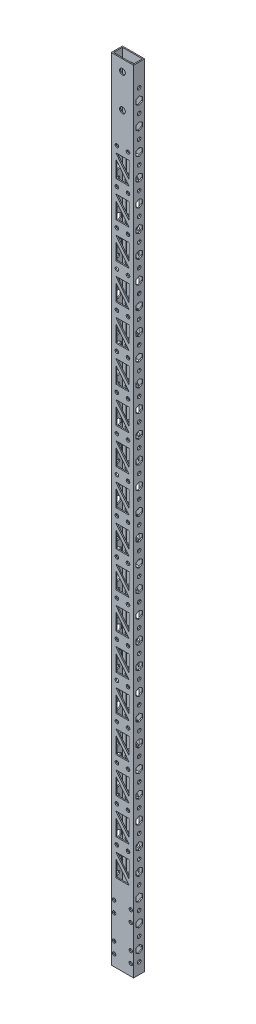
SolidWorks part; units mm, degrees
ref_plane "前视基准面" through (0, 0, 0) normal (0, 0, 1) x (1, 0, 0)
ref_plane "上视基准面" through (0, 0, 0) normal (0, 1, 0) x (1, 0, 0)
ref_plane "右视基准面" through (0, 0, 0) normal (1, 0, 0) x (0, 0, -1)
other "Configuration Table"
sketch "草图1" plane through (0, 0, 0) normal (0, 1, 0) x (1, 0, 0)
  line L1 (-10, -5) -> (10, -5)
  line L2 (-10, -5) -> (-10, 5)
  line L3 (-10, 5) -> (10, 5)
  line L4 (10, -5) -> (10, 5)
  line L5 (-10, -5) -> (10, 5) construction
  line L6 (-10, 5) -> (10, -5) construction
  point P0 (0, 0)
  dimension "D1" = 20
  dimension "D2" = 10
extrude "拉伸-薄壁1" add sketch "草图1" along normal blind 710 thin thin type one direction reverse wall 1
sketch "草图2" plane through (0, 0, -5) normal (0, 0, -1) x (-1, 0, 0)
  line L0 (-10, 710) -> (-10, 0) construction
  line L1 (10, 0) -> (-10, 0) construction
  line L2 (10, 0) -> (10, 30) construction
  line L3 (10, 30) -> (-10, 30) construction
  line L4 (-10, 0) -> (-10, 30) construction
  line L5 (-10, 15) -> (10, 15) construction
  line L6 (0, 0) -> (0, 30) construction
  line L7 (-10, 46.9) -> (10, 46.9) construction
  line L8 (-10, 700) -> (10, 700) construction
  line L9 (10, 710) -> (10, 0) construction
  line L10 (0, 710) -> (0, 700) construction
  line L11 (-10, 710) -> (10, 710) construction
  line L12 (0, 700) -> (0, 670) construction
  circle A0 centre (-7.5, 20) radius 1.55
  circle A1 centre (-7.5, 10) radius 1.55
  circle A2 centre (7.5, 10) radius 1.55
  circle A3 centre (7.5, 20) radius 1.55
  circle A4 centre (-7.5, 51.9) radius 1.55
  circle A5 centre (-7.5, 41.9) radius 1.55
  circle A6 centre (7.5, 41.9) radius 1.55
  circle A7 centre (7.5, 51.9) radius 1.55
  circle A12 centre (0, 700) radius 2.6
  circle A13 centre (0, 670) radius 2.6
  dimension "D2" = 3.1
  dimension "D7" = 5.2
  dimension "D1" = 30
  dimension "D3" = 15
  dimension "D4" = 10
  dimension "D6" = 31.9
  dimension "D8" = 30
  dimension "D10" = 10
  dimension "D5" = 2
extrude "切除-拉伸1" cut sketch "草图2" against normal through all
sketch "草图3" plane through (-10, 0, 0) normal (-1, 0, 0) x (0, 0, 1)
  line L0 (-5, 0) -> (5, 0) construction
  line L1 (0, 10) -> (0, 0) construction
  line L2 (0, 690) -> (0, 670) construction
  line L3 (-3.0311, 681.75) -> (-3.0311, 678.25)
  line L4 (-3.0311, 678.25) -> (0, 676.5)
  line L5 (0, 676.5) -> (3.0311, 678.25)
  line L6 (3.0311, 678.25) -> (3.0311, 681.75)
  line L7 (3.0311, 681.75) -> (0, 683.5)
  line L8 (0, 683.5) -> (-3.0311, 681.75)
  line L9 (3.0311, 661.75) -> (0, 663.5)
  line L10 (0, 663.5) -> (-3.0311, 661.75)
  line L11 (-3.0311, 661.75) -> (-3.0311, 658.25)
  line L12 (-3.0311, 658.25) -> (0, 656.5)
  line L13 (3.0311, 658.25) -> (3.0311, 661.75)
  line L14 (0, 656.5) -> (3.0311, 658.25)
  line L15 (3.0311, 641.75) -> (0, 643.5)
  line L16 (0, 643.5) -> (-3.0311, 641.75)
  line L17 (-3.0311, 641.75) -> (-3.0311, 638.25)
  line L18 (-3.0311, 638.25) -> (0, 636.5)
  line L19 (3.0311, 638.25) -> (3.0311, 641.75)
  line L20 (0, 636.5) -> (3.0311, 638.25)
  line L21 (3.0311, 621.75) -> (0, 623.5)
  line L22 (0, 623.5) -> (-3.0311, 621.75)
  line L23 (-3.0311, 621.75) -> (-3.0311, 618.25)
  line L24 (-3.0311, 618.25) -> (0, 616.5)
  line L25 (3.0311, 618.25) -> (3.0311, 621.75)
  line L26 (0, 616.5) -> (3.0311, 618.25)
  line L27 (3.0311, 601.75) -> (0, 603.5)
  line L28 (0, 603.5) -> (-3.0311, 601.75)
  line L29 (-3.0311, 601.75) -> (-3.0311, 598.25)
  line L30 (-3.0311, 598.25) -> (0, 596.5)
  line L31 (3.0311, 598.25) -> (3.0311, 601.75)
  line L32 (0, 596.5) -> (3.0311, 598.25)
  line L33 (3.0311, 581.75) -> (0, 583.5)
  line L34 (0, 583.5) -> (-3.0311, 581.75)
  line L35 (-3.0311, 581.75) -> (-3.0311, 578.25)
  line L36 (-3.0311, 578.25) -> (0, 576.5)
  line L37 (3.0311, 578.25) -> (3.0311, 581.75)
  line L38 (0, 576.5) -> (3.0311, 578.25)
  line L39 (3.0311, 561.75) -> (0, 563.5)
  line L40 (0, 563.5) -> (-3.0311, 561.75)
  line L41 (-3.0311, 561.75) -> (-3.0311, 558.25)
  line L42 (-3.0311, 558.25) -> (0, 556.5)
  line L43 (3.0311, 558.25) -> (3.0311, 561.75)
  line L44 (0, 556.5) -> (3.0311, 558.25)
  line L45 (3.0311, 541.75) -> (0, 543.5)
  line L46 (0, 543.5) -> (-3.0311, 541.75)
  line L47 (-3.0311, 541.75) -> (-3.0311, 538.25)
  line L48 (-3.0311, 538.25) -> (0, 536.5)
  line L49 (3.0311, 538.25) -> (3.0311, 541.75)
  line L50 (0, 536.5) -> (3.0311, 538.25)
  line L51 (3.0311, 521.75) -> (0, 523.5)
  line L52 (0, 523.5) -> (-3.0311, 521.75)
  line L53 (-3.0311, 521.75) -> (-3.0311, 518.25)
  line L54 (-3.0311, 518.25) -> (0, 516.5)
  line L55 (3.0311, 518.25) -> (3.0311, 521.75)
  line L56 (0, 516.5) -> (3.0311, 518.25)
  line L57 (3.0311, 501.75) -> (0, 503.5)
  line L58 (0, 503.5) -> (-3.0311, 501.75)
  line L59 (-3.0311, 501.75) -> (-3.0311, 498.25)
  line L60 (-3.0311, 498.25) -> (0, 496.5)
  line L61 (3.0311, 498.25) -> (3.0311, 501.75)
  line L62 (0, 496.5) -> (3.0311, 498.25)
  line L63 (3.0311, 481.75) -> (0, 483.5)
  line L64 (0, 483.5) -> (-3.0311, 481.75)
  line L65 (-3.0311, 481.75) -> (-3.0311, 478.25)
  line L66 (-3.0311, 478.25) -> (0, 476.5)
  line L67 (3.0311, 478.25) -> (3.0311, 481.75)
  line L68 (0, 476.5) -> (3.0311, 478.25)
  line L69 (3.0311, 461.75) -> (0, 463.5)
  line L70 (0, 463.5) -> (-3.0311, 461.75)
  line L71 (-3.0311, 461.75) -> (-3.0311, 458.25)
  line L72 (-3.0311, 458.25) -> (0, 456.5)
  line L73 (3.0311, 458.25) -> (3.0311, 461.75)
  line L74 (0, 456.5) -> (3.0311, 458.25)
  line L75 (3.0311, 441.75) -> (0, 443.5)
  line L76 (0, 443.5) -> (-3.0311, 441.75)
  line L77 (-3.0311, 441.75) -> (-3.0311, 438.25)
  line L78 (-3.0311, 438.25) -> (0, 436.5)
  line L79 (3.0311, 438.25) -> (3.0311, 441.75)
  line L80 (0, 436.5) -> (3.0311, 438.25)
  line L81 (3.0311, 421.75) -> (0, 423.5)
  line L82 (0, 423.5) -> (-3.0311, 421.75)
  line L83 (-3.0311, 421.75) -> (-3.0311, 418.25)
  line L84 (-3.0311, 418.25) -> (0, 416.5)
  line L85 (3.0311, 418.25) -> (3.0311, 421.75)
  line L86 (0, 416.5) -> (3.0311, 418.25)
  line L87 (3.0311, 401.75) -> (0, 403.5)
  line L88 (0, 403.5) -> (-3.0311, 401.75)
  line L89 (-3.0311, 401.75) -> (-3.0311, 398.25)
  line L90 (-3.0311, 398.25) -> (0, 396.5)
  line L91 (3.0311, 398.25) -> (3.0311, 401.75)
  line L92 (0, 396.5) -> (3.0311, 398.25)
  line L93 (3.0311, 381.75) -> (0, 383.5)
  line L94 (0, 383.5) -> (-3.0311, 381.75)
  line L95 (-3.0311, 381.75) -> (-3.0311, 378.25)
  line L96 (-3.0311, 378.25) -> (0, 376.5)
  line L97 (3.0311, 378.25) -> (3.0311, 381.75)
  line L98 (0, 376.5) -> (3.0311, 378.25)
  line L99 (3.0311, 361.75) -> (0, 363.5)
  line L100 (0, 363.5) -> (-3.0311, 361.75)
  line L101 (-3.0311, 361.75) -> (-3.0311, 358.25)
  line L102 (-3.0311, 358.25) -> (0, 356.5)
  line L103 (3.0311, 358.25) -> (3.0311, 361.75)
  line L104 (0, 356.5) -> (3.0311, 358.25)
  line L105 (3.0311, 341.75) -> (0, 343.5)
  line L106 (0, 343.5) -> (-3.0311, 341.75)
  line L107 (-3.0311, 341.75) -> (-3.0311, 338.25)
  line L108 (-3.0311, 338.25) -> (0, 336.5)
  line L109 (3.0311, 338.25) -> (3.0311, 341.75)
  line L110 (0, 336.5) -> (3.0311, 338.25)
  line L111 (3.0311, 321.75) -> (0, 323.5)
  line L112 (0, 323.5) -> (-3.0311, 321.75)
  line L113 (-3.0311, 321.75) -> (-3.0311, 318.25)
  line L114 (-3.0311, 318.25) -> (0, 316.5)
  line L115 (3.0311, 318.25) -> (3.0311, 321.75)
  line L116 (0, 316.5) -> (3.0311, 318.25)
  line L117 (3.0311, 301.75) -> (0, 303.5)
  line L118 (0, 303.5) -> (-3.0311, 301.75)
  line L119 (-3.0311, 301.75) -> (-3.0311, 298.25)
  line L120 (-3.0311, 298.25) -> (0, 296.5)
  line L121 (3.0311, 298.25) -> (3.0311, 301.75)
  line L122 (0, 296.5) -> (3.0311, 298.25)
  line L123 (3.0311, 281.75) -> (0, 283.5)
  line L124 (0, 283.5) -> (-3.0311, 281.75)
  line L125 (-3.0311, 281.75) -> (-3.0311, 278.25)
  line L126 (-3.0311, 278.25) -> (0, 276.5)
  line L127 (3.0311, 278.25) -> (3.0311, 281.75)
  line L128 (0, 276.5) -> (3.0311, 278.25)
  line L129 (3.0311, 261.75) -> (0, 263.5)
  line L130 (0, 263.5) -> (-3.0311, 261.75)
  line L131 (-3.0311, 261.75) -> (-3.0311, 258.25)
  line L132 (-3.0311, 258.25) -> (0, 256.5)
  line L133 (3.0311, 258.25) -> (3.0311, 261.75)
  line L134 (0, 256.5) -> (3.0311, 258.25)
  line L135 (3.0311, 241.75) -> (0, 243.5)
  line L136 (0, 243.5) -> (-3.0311, 241.75)
  line L137 (-3.0311, 241.75) -> (-3.0311, 238.25)
  line L138 (-3.0311, 238.25) -> (0, 236.5)
  line L139 (3.0311, 238.25) -> (3.0311, 241.75)
  line L140 (0, 236.5) -> (3.0311, 238.25)
  line L141 (3.0311, 221.75) -> (0, 223.5)
  line L142 (0, 223.5) -> (-3.0311, 221.75)
  line L143 (-3.0311, 221.75) -> (-3.0311, 218.25)
  line L144 (-3.0311, 218.25) -> (0, 216.5)
  line L145 (3.0311, 218.25) -> (3.0311, 221.75)
  line L146 (0, 216.5) -> (3.0311, 218.25)
  line L147 (3.0311, 201.75) -> (0, 203.5)
  line L148 (0, 203.5) -> (-3.0311, 201.75)
  line L149 (-3.0311, 201.75) -> (-3.0311, 198.25)
  line L150 (-3.0311, 198.25) -> (0, 196.5)
  line L151 (3.0311, 198.25) -> (3.0311, 201.75)
  line L152 (0, 196.5) -> (3.0311, 198.25)
  line L153 (3.0311, 181.75) -> (0, 183.5)
  line L154 (0, 183.5) -> (-3.0311, 181.75)
  line L155 (-3.0311, 181.75) -> (-3.0311, 178.25)
  line L156 (-3.0311, 178.25) -> (0, 176.5)
  line L157 (3.0311, 178.25) -> (3.0311, 181.75)
  line L158 (0, 176.5) -> (3.0311, 178.25)
  line L159 (3.0311, 161.75) -> (0, 163.5)
  line L160 (0, 163.5) -> (-3.0311, 161.75)
  line L161 (-3.0311, 161.75) -> (-3.0311, 158.25)
  line L162 (-3.0311, 158.25) -> (0, 156.5)
  line L163 (3.0311, 158.25) -> (3.0311, 161.75)
  line L164 (0, 156.5) -> (3.0311, 158.25)
  line L165 (3.0311, 141.75) -> (0, 143.5)
  line L166 (0, 143.5) -> (-3.0311, 141.75)
  line L167 (-3.0311, 141.75) -> (-3.0311, 138.25)
  line L168 (-3.0311, 138.25) -> (0, 136.5)
  line L169 (3.0311, 138.25) -> (3.0311, 141.75)
  line L170 (0, 136.5) -> (3.0311, 138.25)
  line L171 (3.0311, 121.75) -> (0, 123.5)
  line L172 (0, 123.5) -> (-3.0311, 121.75)
  line L173 (-3.0311, 121.75) -> (-3.0311, 118.25)
  line L174 (-3.0311, 118.25) -> (0, 116.5)
  line L175 (3.0311, 118.25) -> (3.0311, 121.75)
  line L176 (0, 116.5) -> (3.0311, 118.25)
  line L177 (3.0311, 101.75) -> (0, 103.5)
  line L178 (0, 103.5) -> (-3.0311, 101.75)
  line L179 (-3.0311, 101.75) -> (-3.0311, 98.25)
  line L180 (-3.0311, 98.25) -> (0, 96.5)
  line L181 (3.0311, 98.25) -> (3.0311, 101.75)
  line L182 (0, 96.5) -> (3.0311, 98.25)
  line L183 (3.0311, 81.75) -> (0, 83.5)
  line L184 (0, 83.5) -> (-3.0311, 81.75)
  line L185 (-3.0311, 81.75) -> (-3.0311, 78.25)
  line L186 (-3.0311, 78.25) -> (0, 76.5)
  line L187 (3.0311, 78.25) -> (3.0311, 81.75)
  line L188 (0, 76.5) -> (3.0311, 78.25)
  line L189 (3.0311, 61.75) -> (0, 63.5)
  line L190 (0, 63.5) -> (-3.0311, 61.75)
  line L191 (-3.0311, 61.75) -> (-3.0311, 58.25)
  line L192 (-3.0311, 58.25) -> (0, 56.5)
  line L193 (3.0311, 58.25) -> (3.0311, 61.75)
  line L194 (0, 56.5) -> (3.0311, 58.25)
  line L195 (3.0311, 41.75) -> (0, 43.5)
  line L196 (0, 43.5) -> (-3.0311, 41.75)
  line L197 (-3.0311, 41.75) -> (-3.0311, 38.25)
  line L198 (-3.0311, 38.25) -> (0, 36.5)
  line L199 (3.0311, 38.25) -> (3.0311, 41.75)
  line L200 (0, 36.5) -> (3.0311, 38.25)
  line L201 (3.0311, 21.75) -> (0, 23.5)
  line L202 (0, 23.5) -> (-3.0311, 21.75)
  line L203 (-3.0311, 21.75) -> (-3.0311, 18.25)
  line L204 (-3.0311, 18.25) -> (0, 16.5)
  line L205 (3.0311, 18.25) -> (3.0311, 21.75)
  line L206 (0, 16.5) -> (3.0311, 18.25)
  circle A0 centre (0, 10) radius 1.6
  circle A1 centre (0, 30) radius 1.6
  circle A2 centre (0, 50) radius 1.6
  circle A3 centre (0, 70) radius 1.6
  circle A4 centre (0, 90) radius 1.6
  circle A5 centre (0, 110) radius 1.6
  circle A6 centre (0, 130) radius 1.6
  circle A7 centre (0, 150) radius 1.6
  circle A8 centre (0, 170) radius 1.6
  circle A9 centre (0, 190) radius 1.6
  circle A10 centre (0, 210) radius 1.6
  circle A11 centre (0, 230) radius 1.6
  circle A12 centre (0, 250) radius 1.6
  circle A13 centre (0, 270) radius 1.6
  circle A14 centre (0, 290) radius 1.6
  circle A15 centre (0, 310) radius 1.6
  circle A16 centre (0, 330) radius 1.6
  circle A17 centre (0, 350) radius 1.6
  circle A18 centre (0, 370) radius 1.6
  circle A19 centre (0, 390) radius 1.6
  circle A20 centre (0, 410) radius 1.6
  circle A21 centre (0, 430) radius 1.6
  circle A22 centre (0, 450) radius 1.6
  circle A23 centre (0, 470) radius 1.6
  circle A24 centre (0, 490) radius 1.6
  circle A25 centre (0, 510) radius 1.6
  circle A26 centre (0, 530) radius 1.6
  circle A27 centre (0, 550) radius 1.6
  circle A28 centre (0, 570) radius 1.6
  circle A29 centre (0, 590) radius 1.6
  circle A30 centre (0, 610) radius 1.6
  circle A31 centre (0, 630) radius 1.6
  circle A32 centre (0, 650) radius 1.6
  circle A33 centre (0, 670) radius 1.6
  circle A34 centre (0, 690) radius 1.6
  circle A35 centre (0, 680) radius 3.0311 construction
  circle A36 centre (0, 660) radius 3.0311 construction
  circle A37 centre (0, 640) radius 3.0311 construction
  circle A38 centre (0, 620) radius 3.0311 construction
  circle A39 centre (0, 600) radius 3.0311 construction
  circle A40 centre (0, 580) radius 3.0311 construction
  circle A41 centre (0, 560) radius 3.0311 construction
  circle A42 centre (0, 540) radius 3.0311 construction
  circle A43 centre (0, 520) radius 3.0311 construction
  circle A44 centre (0, 500) radius 3.0311 construction
  circle A45 centre (0, 480) radius 3.0311 construction
  circle A46 centre (0, 460) radius 3.0311 construction
  circle A47 centre (0, 440) radius 3.0311 construction
  circle A48 centre (0, 420) radius 3.0311 construction
  circle A49 centre (0, 400) radius 3.0311 construction
  circle A50 centre (0, 380) radius 3.0311 construction
  circle A51 centre (0, 360) radius 3.0311 construction
  circle A52 centre (0, 340) radius 3.0311 construction
  circle A53 centre (0, 320) radius 3.0311 construction
  circle A54 centre (0, 300) radius 3.0311 construction
  circle A55 centre (0, 280) radius 3.0311 construction
  circle A56 centre (0, 260) radius 3.0311 construction
  circle A57 centre (0, 240) radius 3.0311 construction
  circle A58 centre (0, 220) radius 3.0311 construction
  circle A59 centre (0, 200) radius 3.0311 construction
  circle A60 centre (0, 180) radius 3.0311 construction
  circle A61 centre (0, 160) radius 3.0311 construction
  circle A62 centre (0, 140) radius 3.0311 construction
  circle A63 centre (0, 120) radius 3.0311 construction
  circle A64 centre (0, 100) radius 3.0311 construction
  circle A65 centre (0, 80) radius 3.0311 construction
  circle A66 centre (0, 60) radius 3.0311 construction
  circle A67 centre (0, 40) radius 3.0311 construction
  circle A68 centre (0, 20) radius 3.0311 construction
  dimension "D1" = 3.2
  dimension "D2" = 10
  dimension "D4" = 20
  dimension "D5" = 3.5
  dimension "D6" = 10
  dimension "D8" = 20
  dimension "D3" = 35
  dimension "D7" = 34
extrude "切除-拉伸2" cut sketch "草图3" against normal through all
sketch "草图6" plane through (0, 0, -5) normal (0, 0, -1) x (-1, 0, 0)
  line L0 (-6, 70) -> (6, 70)
  line L3 (0, 275) -> (0, 294.634) construction
  line L197 (6, 70) -> (6, 85)
  line L198 (6, 85) -> (-6, 70)
  line L199 (-10, 0) -> (10, 0) construction
  line L200 (-6, 75) -> (-6, 90)
  line L201 (-6, 90) -> (6, 90)
  line L202 (6, 90) -> (-6, 75)
  line L203 (6, 102) -> (6, 117)
  line L204 (-6, 102) -> (6, 102)
  line L205 (6, 117) -> (-6, 102)
  line L206 (6, 122) -> (-6, 107)
  line L207 (-6, 122) -> (6, 122)
  line L208 (-6, 107) -> (-6, 122)
  line L209 (6, 134) -> (6, 149)
  line L210 (-6, 134) -> (6, 134)
  line L211 (6, 149) -> (-6, 134)
  line L212 (6, 154) -> (-6, 139)
  line L213 (-6, 154) -> (6, 154)
  line L214 (-6, 139) -> (-6, 154)
  line L215 (6, 166) -> (6, 181)
  line L216 (-6, 166) -> (6, 166)
  line L217 (6, 181) -> (-6, 166)
  line L218 (6, 186) -> (-6, 171)
  line L219 (-6, 186) -> (6, 186)
  line L220 (-6, 171) -> (-6, 186)
  line L221 (6, 198) -> (6, 213)
  line L222 (-6, 198) -> (6, 198)
  line L223 (6, 213) -> (-6, 198)
  line L224 (6, 218) -> (-6, 203)
  line L225 (-6, 218) -> (6, 218)
  line L226 (-6, 203) -> (-6, 218)
  line L227 (6, 230) -> (6, 245)
  line L228 (-6, 230) -> (6, 230)
  line L229 (6, 245) -> (-6, 230)
  line L230 (6, 250) -> (-6, 235)
  line L231 (-6, 250) -> (6, 250)
  line L232 (-6, 235) -> (-6, 250)
  line L233 (6, 262) -> (6, 277)
  line L234 (-6, 262) -> (6, 262)
  line L235 (6, 277) -> (-6, 262)
  line L236 (6, 282) -> (-6, 267)
  line L237 (-6, 282) -> (6, 282)
  line L238 (-6, 267) -> (-6, 282)
  line L239 (6, 294) -> (6, 309)
  line L240 (-6, 294) -> (6, 294)
  line L241 (6, 309) -> (-6, 294)
  line L242 (6, 314) -> (-6, 299)
  line L243 (-6, 314) -> (6, 314)
  line L244 (-6, 299) -> (-6, 314)
  line L245 (6, 326) -> (6, 341)
  line L246 (-6, 326) -> (6, 326)
  line L247 (6, 341) -> (-6, 326)
  line L248 (6, 346) -> (-6, 331)
  line L249 (-6, 346) -> (6, 346)
  line L250 (-6, 331) -> (-6, 346)
  line L251 (6, 358) -> (6, 373)
  line L252 (-6, 358) -> (6, 358)
  line L253 (6, 373) -> (-6, 358)
  line L254 (6, 378) -> (-6, 363)
  line L255 (-6, 378) -> (6, 378)
  line L256 (-6, 363) -> (-6, 378)
  line L257 (6, 390) -> (6, 405)
  line L258 (-6, 390) -> (6, 390)
  line L259 (6, 405) -> (-6, 390)
  line L260 (6, 410) -> (-6, 395)
  line L261 (-6, 410) -> (6, 410)
  line L262 (-6, 395) -> (-6, 410)
  line L263 (6, 422) -> (6, 437)
  line L264 (-6, 422) -> (6, 422)
  line L265 (6, 437) -> (-6, 422)
  line L266 (6, 442) -> (-6, 427)
  line L267 (-6, 442) -> (6, 442)
  line L268 (-6, 427) -> (-6, 442)
  line L269 (6, 454) -> (6, 469)
  line L270 (-6, 454) -> (6, 454)
  line L271 (6, 469) -> (-6, 454)
  line L272 (6, 474) -> (-6, 459)
  line L273 (-6, 474) -> (6, 474)
  line L274 (-6, 459) -> (-6, 474)
  line L275 (6, 486) -> (6, 501)
  line L276 (-6, 486) -> (6, 486)
  line L277 (6, 501) -> (-6, 486)
  line L278 (6, 506) -> (-6, 491)
  line L279 (-6, 506) -> (6, 506)
  line L280 (-6, 491) -> (-6, 506)
  line L281 (6, 518) -> (6, 533)
  line L282 (-6, 518) -> (6, 518)
  line L283 (6, 533) -> (-6, 518)
  line L284 (6, 538) -> (-6, 523)
  line L285 (-6, 538) -> (6, 538)
  line L286 (-6, 523) -> (-6, 538)
  line L287 (6, 550) -> (6, 565)
  line L288 (-6, 550) -> (6, 550)
  line L289 (6, 565) -> (-6, 550)
  line L290 (6, 570) -> (-6, 555)
  line L291 (-6, 570) -> (6, 570)
  line L292 (-6, 555) -> (-6, 570)
  line L293 (6, 582) -> (6, 597)
  line L294 (-6, 582) -> (6, 582)
  line L295 (6, 597) -> (-6, 582)
  line L296 (6, 602) -> (-6, 587)
  line L297 (-6, 602) -> (6, 602)
  line L298 (-6, 587) -> (-6, 602)
  line L299 (6, 614) -> (6, 629)
  line L300 (-6, 614) -> (6, 614)
  line L301 (6, 629) -> (-6, 614)
  line L302 (6, 634) -> (-6, 619)
  line L303 (-6, 634) -> (6, 634)
  line L304 (-6, 619) -> (-6, 634)
  circle A33 centre (-5, 96) radius 1.6
  circle A34 centre (5, 96) radius 1.6
  circle A35 centre (-5, 128) radius 1.6
  circle A36 centre (5, 128) radius 1.6
  circle A37 centre (-5, 160) radius 1.6
  circle A38 centre (5, 160) radius 1.6
  circle A39 centre (-5, 192) radius 1.6
  circle A40 centre (5, 192) radius 1.6
  circle A41 centre (-5, 224) radius 1.6
  circle A42 centre (5, 224) radius 1.6
  circle A43 centre (-5, 256) radius 1.6
  circle A44 centre (5, 256) radius 1.6
  circle A45 centre (-5, 288) radius 1.6
  circle A46 centre (5, 288) radius 1.6
  circle A47 centre (-5, 320) radius 1.6
  circle A48 centre (5, 320) radius 1.6
  circle A49 centre (-5, 352) radius 1.6
  circle A50 centre (5, 352) radius 1.6
  circle A51 centre (-5, 384) radius 1.6
  circle A52 centre (5, 384) radius 1.6
  circle A53 centre (-5, 416) radius 1.6
  circle A54 centre (5, 416) radius 1.6
  circle A55 centre (-5, 448) radius 1.6
  circle A56 centre (5, 448) radius 1.6
  circle A57 centre (-5, 480) radius 1.6
  circle A58 centre (5, 480) radius 1.6
  circle A59 centre (-5, 512) radius 1.6
  circle A60 centre (5, 512) radius 1.6
  circle A61 centre (-5, 544) radius 1.6
  circle A62 centre (5, 544) radius 1.6
  circle A63 centre (-5, 576) radius 1.6
  circle A64 centre (5, 576) radius 1.6
  circle A92 centre (-5, 608) radius 1.6
  circle A93 centre (5, 608) radius 1.6
  circle A94 centre (-5, 640) radius 1.6
  circle A95 centre (5, 640) radius 1.6
  dimension "D1" = 70
  dimension "D2" = 12
  dimension "D3" = 15
  dimension "D8" = 3.2
  dimension "D4" = 15
  dimension "D5" = 20
  dimension "D6" = 18
  dimension "D9" = 6
  dimension "D10" = 5
  dimension "D11" = 32
  dimension "D7" = 32
extrude "切除-拉伸4" cut sketch "草图6" against normal through all
